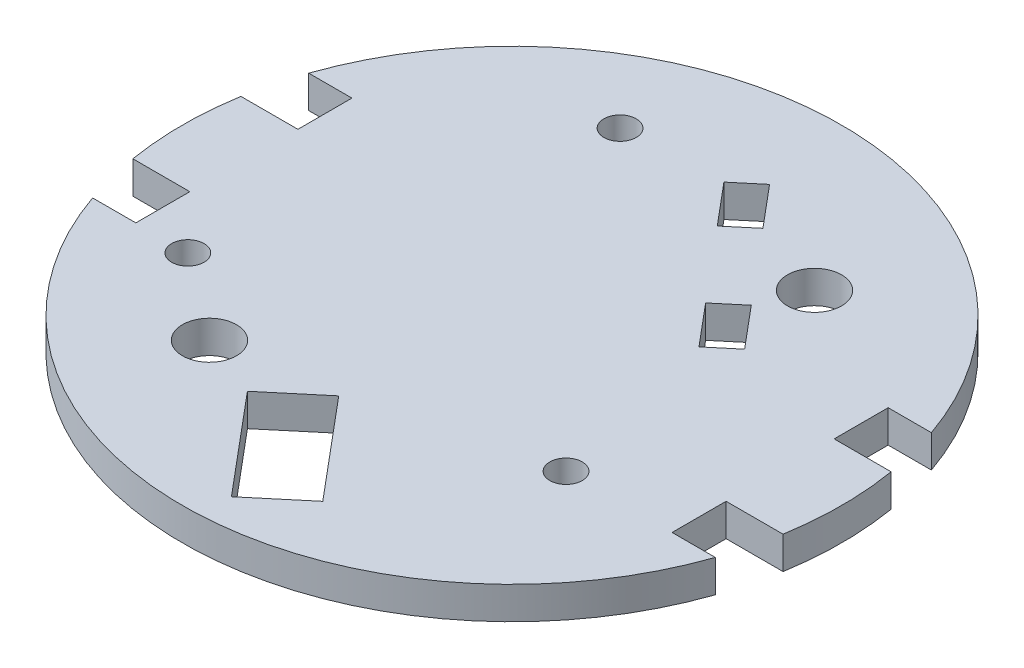
SolidWorks part; units mm, degrees
ref_plane "Alzado" through (0, 0, 0) normal (0, 0, 1) x (1, 0, 0)
ref_plane "Planta" through (0, 0, 0) normal (0, 1, 0) x (1, 0, 0)
ref_plane "Vista lateral" through (0, 0, 0) normal (1, 0, 0) x (0, 0, -1)
sketch "Croquis1" plane through (0, 0, 0) normal (0, 1, 0) x (1, 0, 0)
  circle A0 centre (0, 0) radius 30.5
extrude "Saliente-Extruir1" add sketch "Croquis1" along normal blind 3
sketch "Croquis5" plane through (0, 3, 0) normal (0, 1, 0) x (1, 0, 0)
  line L0 (0, 0) -> (0, 10)
  line L1 (28.8141, -5) -> (30.0874, -5)
  line L2 (28.8141, 5) -> (30.0874, 5)
  line L3 (-24.8141, 10) -> (-28.8141, 10)
  line L4 (24.8141, -5) -> (24.8141, -10)
  line L5 (-24.8141, -10) -> (-28.8141, -10)
  line L6 (24.8141, -5) -> (28.8141, -5)
  line L7 (24.8141, 5) -> (24.8141, 10)
  line L8 (-24.8141, 5) -> (-28.8141, 5)
  line L9 (-24.8141, 5) -> (-24.8141, 10)
  line L10 (-24.8141, -5) -> (-28.8141, -5)
  line L11 (-24.8141, -5) -> (-24.8141, -10)
  line L12 (24.8141, 5) -> (28.8141, 5)
  line L13 (24.8141, -10) -> (28.8141, -10)
  line L14 (24.8141, 10) -> (28.8141, 10)
  line L15 (-28.8141, 5) -> (-30.0874, 5)
  line L16 (-28.8141, -5) -> (-30.0874, -5)
  circle A1 centre (0, 0) radius 30.5 construction
  arc A2 (-28.8141, 10) -> (-30.0874, 5) centre (0, 0) ccw
  arc A3 (28.8141, 10) -> (28.8141, -10) centre (0, 0) cw
  arc A4 (-30.0874, -5) -> (-28.8141, -10) centre (0, 0) ccw
  arc A5 (30.0874, -5) -> (28.8141, -10) centre (0, 0) cw
  arc A6 (28.8141, 10) -> (30.0874, 5) centre (0, 0) cw
  circle M2 centre (0, 0) radius 30.5
extrude "Cortar-Extruir3" cut sketch "Croquis5" against normal blind 4 contours L11 L10 L8 L9 L3 L5 M2 | L15 L8 L9 L3 M2 | L14 L7 L12 L2 M2 | L4 L13 L1 L6 M2 region at (27.1844, 3, 7.3876) region at (27.1844, 3, -7.3876) region at (-27.1844, 3, 7.3876) region at (-27.1844, 3, -7.3876)
sketch "Croquis7" plane through (0, 3, 0) normal (0, 1, 0) x (1, 0, 0)
  line L0 (-8.1011, 29.1011) -> (9.5756, 8.0348)
  line L1 (9.5756, 8.0348) -> (27.2522, -13.0314)
  line L2 (-8.1011, 29.1011) -> (-27.2522, 13.0314)
  line L3 (27.2522, -13.0314) -> (8.1011, -29.1011)
  line L4 (8.1011, -29.1011) -> (-27.2522, 13.0314)
  line L5 (1.4284, 22.4114) -> (-0.8697, 20.4831)
  line L6 (1.4284, 22.4114) -> (4.6423, 18.5812)
  line L7 (4.6423, 18.5812) -> (2.3442, 16.6528)
  line L8 (2.3442, 16.6528) -> (-0.8697, 20.4831)
  line L9 (7.9686, 9.95) -> (11.1825, 6.1197)
  line L10 (8.1011, -29.1011) -> (5.53, -26.0369)
  line L11 (10.2667, 11.8783) -> (13.4807, 8.0481)
  line L12 (13.4807, 8.0481) -> (11.1825, 6.1197)
  line L13 (10.2667, 11.8783) -> (7.9686, 9.95)
  line L14 (5.53, -26.0369) -> (10.8923, -21.5374)
  line L15 (10.8923, -21.5374) -> (-19.3188, 14.4667)
  line L17 (-24.6811, 9.9672) -> (-19.3188, 14.4667)
  point P7 (-9.5756, -8.0348)
extrude "Cortar-Extruir5" cut sketch "Croquis7" against normal blind 4 contours L7 L6 L5 L0 | L11 L13 L0 L1 L12 region at (1.8863, 3, -19.5321) region at (10.7246, 3, -8.999)
sketch "Croquis8" plane through (0, 3, 0) normal (0, 1, 0) x (1, 0, 0)
  line L0 (-11.3137, 11.3137) -> (0, 0)
  line L2 (0, 0) -> (12, 0)
  line L3 (0, 0) -> (-11.3137, 11.3137)
  line L4 (12, 0) -> (12, 16)
  line L5 (0, 0) -> (-12, 0)
  line L6 (-12, 0) -> (-12, -16)
  line L10 (1.5586, -27.5246) -> (6.1549, -23.6679)
  line L11 (6.1549, -23.6679) -> (-1.5586, -14.4754)
  line L13 (-6.1549, -18.3321) -> (-1.5586, -14.4754)
  line L14 (1.5586, -27.5246) -> (-6.1549, -18.3321)
  circle A0 centre (0, 0) radius 30
  circle A1 centre (0, 0) radius 16
  circle A2 centre (0, 0) radius 24
  circle A3 centre (-12, -16) radius 2.5
  circle A4 centre (0, 0) radius 20
  circle A5 centre (12, 16) radius 2.5
  point P20 (-3.8567, -16.4037)
extrude "Cortar-Extruir6" cut sketch "Croquis8" against normal blind 10 contours L13 A4 L10 L11 | A4 A3 | L6 A4 A3 | A3 A4 L6 | A4 A5 | L4 A5 A4 | A4 A5 L4 | A2 L14 L10 L11 | A4 L14 A2 L11 | L13 A1 L11 region at (10.8019, 3, -15.3654) region at (12.6835, 3, -14.5491) region at (-10.8019, 3, 15.3654) region at (-12.6835, 3, 14.5491) region at (-1.7552, 3, 18.1481) region at (-1.6254, 3, 15.4208) region at (12.6194, 3, -16.8259) region at (-12.6194, 3, 16.8259) region at (0.4942, 3, 21.8146) region at (2.2344, 3, 25.0251)
sketch "Croquis9" plane through (0, 3, 0) normal (0, 1, 0) x (1, 0, 0)
  line L0 (0, 0) -> (0, 20)
  line L1 (0, 20) -> (-10, 20)
  line L2 (0, 0) -> (-20, 0)
  line L3 (-20, 0) -> (-20, -10)
  line L4 (0, 0) -> (15, 0)
  line L5 (15, 0) -> (15, -10)
  circle A0 centre (-10, 20) radius 1.5
  circle A1 centre (-20, -10) radius 1.5
  circle A2 centre (15, -10) radius 1.5
extrude "Cortar-Extruir7" cut sketch "Croquis9" against normal blind 3 contours A1 | A2 | A0 region at (-18.9693, 3, 8.9693) region at (16.0307, 3, 8.9693)
